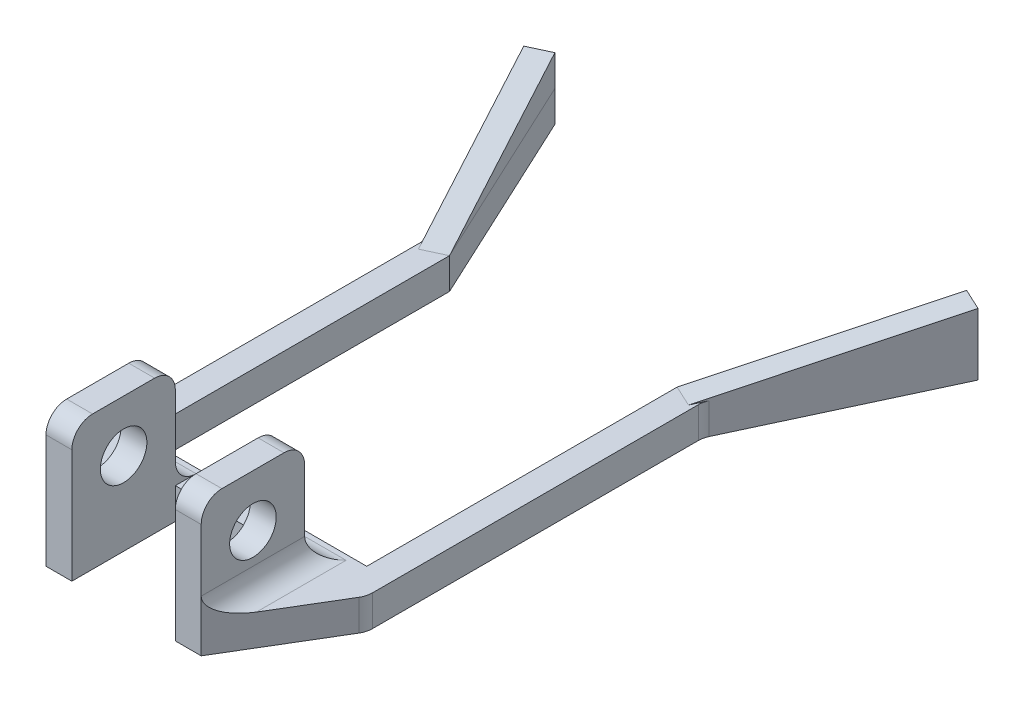
SolidWorks part; units mm, degrees
ref_plane "Front Plane" through (0, 0, 0) normal (0, 0, 1) x (1, 0, 0)
ref_plane "Top Plane" through (0, 0, 0) normal (0, 1, 0) x (1, 0, 0)
ref_plane "Right Plane" through (0, 0, 0) normal (1, 0, 0) x (0, 0, -1)
sketch "Sketch1" plane through (0, 0, 0) normal (0, 1, 0) x (1, 0, 0)
  line L0 (0, -55) -> (0, 55) construction
  line L12 (11, 0) -> (11, 30)
  line L15 (-11, 0) -> (-11, 30)
  line L16 (-11, 0) -> (11, 0)
  line L17 (-13.5, 30) -> (-13.5, -2.5)
  line L18 (13.5, -2.5) -> (13.5, 30)
  line L19 (-11, 30) -> (-19.8989, 49.0837)
  line L20 (-19.8989, 49.0837) -> (-21.9524, 48.1262)
  line L21 (-21.9524, 48.1262) -> (-13.5, 30)
  line L22 (19.8989, 49.0837) -> (21.9524, 48.1262)
  line L23 (21.9524, 48.1262) -> (13.5, 30)
  line L24 (11, 30) -> (19.8989, 49.0837)
  line L25 (5, -2.5) -> (5, -12.5)
  line L26 (5, -12.5) -> (7.5, -12.5)
  line L29 (-5, -2.5) -> (-5, -12.5)
  line L30 (-5, -12.5) -> (-7.5, -12.5)
  line L32 (-5, -2.5) -> (5, -2.5)
  line L33 (7.5, -12.5) -> (13.5, -2.5)
  line L34 (-13.5, -2.5) -> (-7.5, -12.5)
  point P0 (0, 0)
  dimension "D1" = 22
  dimension "D3" = 2.5
  dimension "D4" = 20
  dimension "D5" = 155
  dimension "D6" = 30
  dimension "D7" = 2.5
extrude "Boss-Extrude1" add sketch "Sketch1" along normal blind 3
sketch "Sketch2" plane through (2.4553, 0, -1.1449) normal (0.9063, 0, -0.4226) x (-0.4226, 0, -0.9063)
  line L0 (31.838, 3) -> (52.8946, 6)
  line L1 (52.8946, 6) -> (52.8946, 3)
  line L2 (31.838, 3) -> (52.8946, 3) construction
  line L3 (31.838, 3) -> (52.8946, 3)
  dimension "D1" = 3
extrude "Boss-Extrude2" add sketch "Sketch2" against normal up to surface (2.2658 mm away) separate body up to face at (-17.7262, 1.5, -39.0631)
mirror "Mirror4" about plane through (0, 0, 0) normal (1, 0, 0) of "Boss-Extrude2"
sketch "Sketch3" plane through (0, 3, 0) normal (0, 1, 0) x (1, 0, 0)
  line L0 (-5, -2.5) -> (5, -2.5) construction
  line L23 (5, -12.5) -> (7.5, -12.5) construction
  line L24 (7.5, -12.5) -> (5, -12.5)
  line L25 (7.5, -12.5) -> (7.5, -2.5)
  line L26 (7.5, -2.5) -> (5, -2.5)
  line L27 (5, -12.5) -> (5, -2.5)
  line L28 (5, -2.5) -> (5, -12.5) construction
  line L29 (0, -7.15) -> (0, 7.15) construction
  line L30 (-7.5, -2.5) -> (-5, -2.5)
  line L31 (-5, -12.5) -> (-5, -2.5)
  line L32 (-7.5, -12.5) -> (-5, -12.5)
  line L33 (-7.5, -12.5) -> (-7.5, -2.5)
  line L34 (-13.5, -2.5) -> (-7.5, -12.5) construction
  line L35 (-7.5, -12.5) -> (-5, -12.5) construction
  point P6 (5, -2.5)
  point P15 (-7.5, -12.5)
  point P20 (0, 0)
extrude "Boss-Extrude3" add sketch "Sketch3" along normal blind 10
sketch "Sketch4" plane through (7.5, 0, 0) normal (1, 0, 0) x (0, 0, -1)
  line L0 (-12.5, 13) -> (-2.5, 13) construction
  line L1 (-2.5, 13) -> (-2.5, 3) construction
  circle A0 centre (-7.5, 8) radius 2.25
  point P2 (-7.4109, 7.7926)
  point P5 (-7.5, 13)
  point P8 (-2.5, 8)
  dimension "D1" = 4.5
extrude "Cut-Extrude1" cut sketch "Sketch4" against normal through all
fillet "Fillet1" radius 2 12 edges at (-7.5, 3, 7.5) (7.5, 3, 7.5) (6.25, 3, 2.5) (-6.25, 3, 2.5) (13.5, 1.5, -30) (13.5, 1.5, 2.5) (-13.5, 1.5, -30) (-13.5, 1.5, 2.5) (6.25, 13, 12.5) (6.25, 13, 2.5) (-6.25, 13, 2.5) (-6.25, 13, 12.5)
